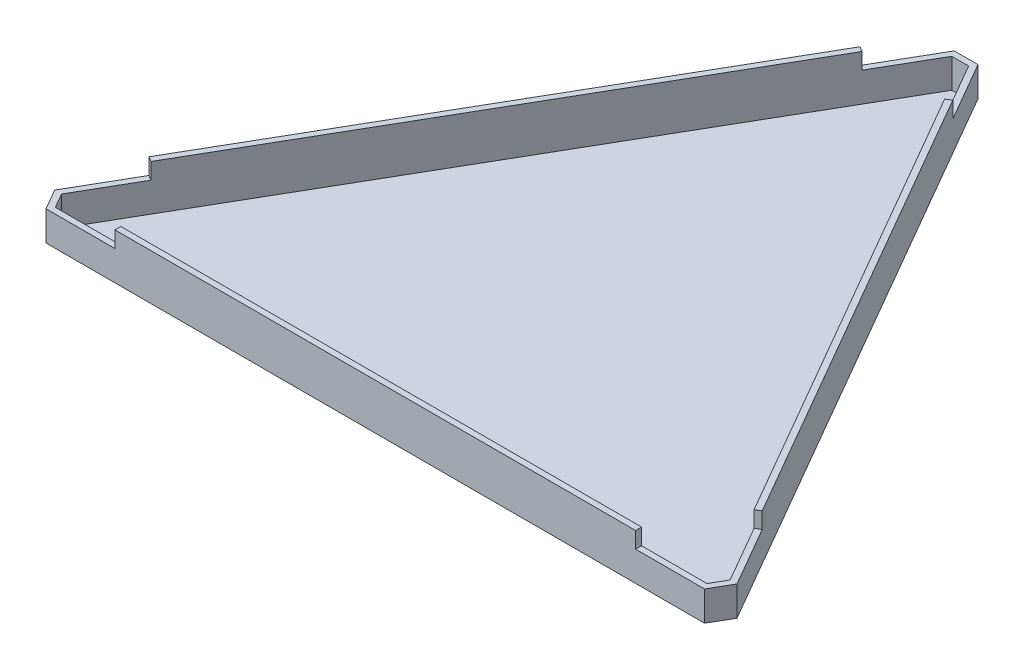
SolidWorks part; units mm, degrees
note: The reader was unsure of these and kept them because the rebuilt part matched: shared geometry of "Sketch1<3>", "Sketch1<4>".
ref_plane "Front Plane" through (0, 0, 0) normal (0, 0, 1) x (1, 0, 0)
ref_plane "Top Plane" through (0, 0, 0) normal (0, 1, 0) x (1, 0, 0)
ref_plane "Right Plane" through (0, 0, 0) normal (1, 0, 0) x (0, 0, -1)
sketch "Sketch1" plane through (0, 0, 0) normal (0, 1, 0) x (1, 0, 0)
  line L7 (-115, 0) -> (-111, -6.9282)
  line L9 (115, 0) -> (111, -6.9282)
  line L17 (-4, 192.2576) -> (111, -6.9282) construction
  line L20 (4, 192.2576) -> (-4, 192.2576)
  line L24 (4, 192.2576) -> (-111, -6.9282) construction
  line L25 (-115, 0) -> (115, 0) construction
  line L26 (-112.6906, 0) -> (-101.6429, 19.1351)
  line L27 (-113, -3.4641) -> (-107, 0) construction
  line L28 (0, 192.2576) -> (0, 185.3294) construction
  line L29 (113, -3.4641) -> (107, 0) construction
  line L30 (59.5, 96.1288) -> (57.7679, 95.1288) construction
  line L31 (-59.5, 96.1288) -> (-57.7679, 95.1288) construction
  line L33 (-112.6906, 0) -> (-109.8453, -4.9282)
  line L36 (112.6906, 0) -> (109.8453, -4.9282)
  line L37 (-2.8453, 190.2576) -> (2.8453, 190.2576)
  line L38 (-87.75, -4.9282) -> (-87.75, -6.9282)
  line L41 (-111, -6.9282) -> (-87.75, -6.9282)
  line L43 (87.75, -6.9282) -> (111, -6.9282)
  line L45 (87.75, -4.9282) -> (87.75, -6.9282)
  line L46 (-87.75, -6.9282) -> (87.75, -6.9282)
  line L49 (-87.75, -4.9282) -> (87.75, -4.9282)
  line L50 (-115, 0) -> (-103.375, 20.1351)
  line L51 (-103.375, 20.1351) -> (-101.6429, 19.1351)
  line L52 (-15.625, 172.1225) -> (-13.8929, 171.1225)
  line L53 (-103.375, 20.1351) -> (-15.625, 172.1225)
  line L54 (-15.625, 172.1225) -> (-4, 192.2576)
  line L55 (-109.8453, -4.9282) -> (-87.75, -4.9282)
  line L56 (109.8453, -4.9282) -> (87.75, -4.9282)
  line L57 (87.75, -6.9282) -> (-87.75, -6.9282)
  line L58 (-13.8929, 171.1225) -> (-101.6429, 19.1351)
  line L59 (-2.8453, 190.2576) -> (-13.8929, 171.1225)
  line L60 (115, 0) -> (103.375, 20.1351)
  line L61 (15.625, 172.1225) -> (13.8929, 171.1225)
  line L62 (103.375, 20.1351) -> (101.6429, 19.1351)
  line L63 (101.6429, 19.1351) -> (112.6906, 0)
  line L64 (2.8453, 190.2576) -> (13.8929, 171.1225)
  line L65 (4, 192.2576) -> (15.625, 172.1225)
  line L66 (15.625, 172.1225) -> (103.375, 20.1351)
  line L67 (101.6429, 19.1351) -> (13.8929, 171.1225)
  point P23 (-57.7679, 95.1288)
  point P28 (57.7679, 95.1288)
  point P29 (58.634, 95.6288)
  point P34 (-58.634, 95.6288)
  point P38 (14.759, 171.6225)
  point P41 (-14.759, 171.6225)
  point P44 (102.509, 19.6351)
  dimension "D1" = 8
  dimension "D2" = 8
  dimension "D3" = 8
  dimension "D4" = 230
  dimension "D5" = 230
  dimension "D6" = 230
  dimension "D8" = 2
  dimension "D9" = 2
extrude "Boss-Extrude1" add sketch "Sketch1" along normal blind 0.08
extrude "Boss-Extrude2" add sketch "Sketch1<3>" along normal blind 10
sketch "Sketch1<3>" plane through (0, 0, 0) normal (0, 1, 0) x (1, 0, 0) same geometry as "Sketch1"
extrude "Boss-Extrude3" add sketch "Sketch1<4>" along normal blind 15.46
sketch "Sketch1<4>" plane through (0, 0, 0) normal (0, 1, 0) x (1, 0, 0) same geometry as "Sketch1"
